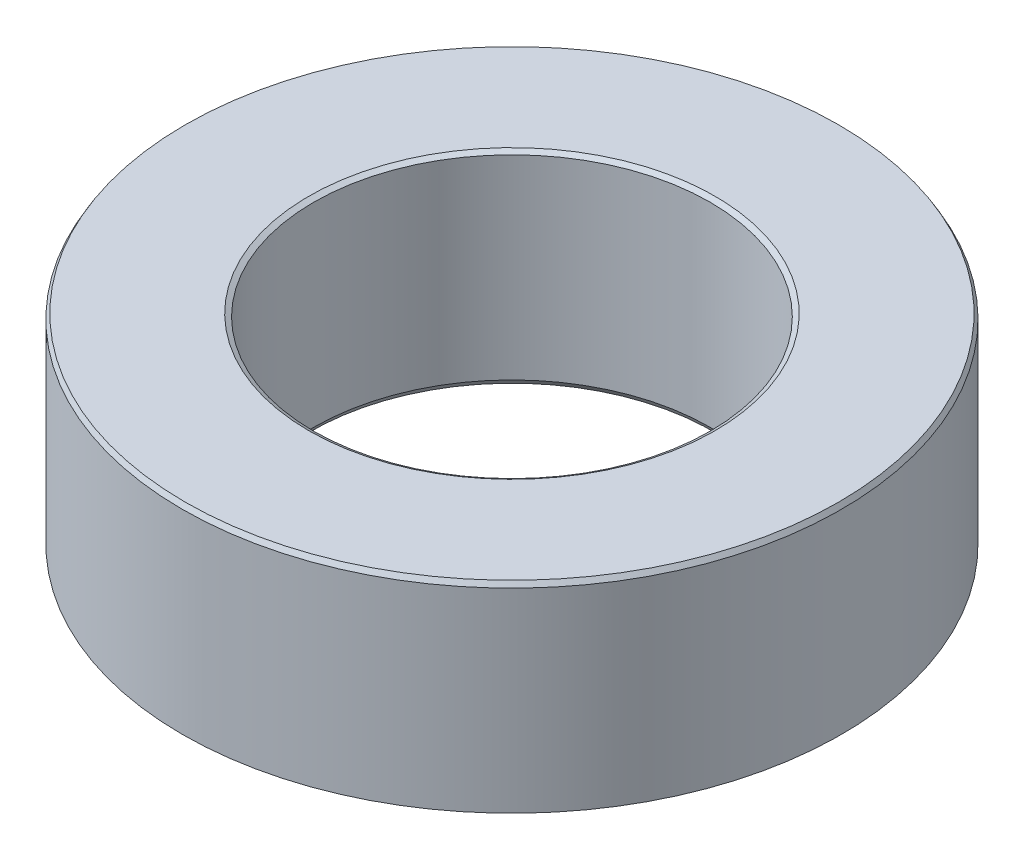
SolidWorks part; units mm, degrees
ref_plane "Front Plane" through (0, 0, 0) normal (0, 0, 1) x (1, 0, 0)
ref_plane "Top Plane" through (0, 0, 0) normal (0, 1, 0) x (1, 0, 0)
ref_plane "Right Plane" through (0, 0, 0) normal (1, 0, 0) x (0, 0, -1)
sketch "Sketch1" plane through (0, 0, 0) normal (0, 1, 0) x (1, 0, 0)
  circle A0 centre (0, 0) radius 25
  dimension "SLEEVE_OD" = 50
extrude "Boss-Extrude1" add sketch "Sketch1" along normal blind 15.3688
sketch "Sketch2" plane through (0, 0, 0) normal (0, 1, 0) x (1, 0, 0)
  circle A0 centre (0, 0) radius 15.0411
  dimension "BORE_D" = 30.0822
extrude "Cut-Extrude1" cut sketch "Sketch2" along normal through all
chamfer "Chamfer1" distance 0.3677 angle 30 4 edges at (0, 15.3688, 15.0411) (0, 0, 15.0411) (0, 0, 25) (0, 15.3688, 25) first distance on face at (0, 15.3688, 15.0411) first distance on face at (0, 0, 15.0411) first distance on face at (0, 15.3688, 25)
